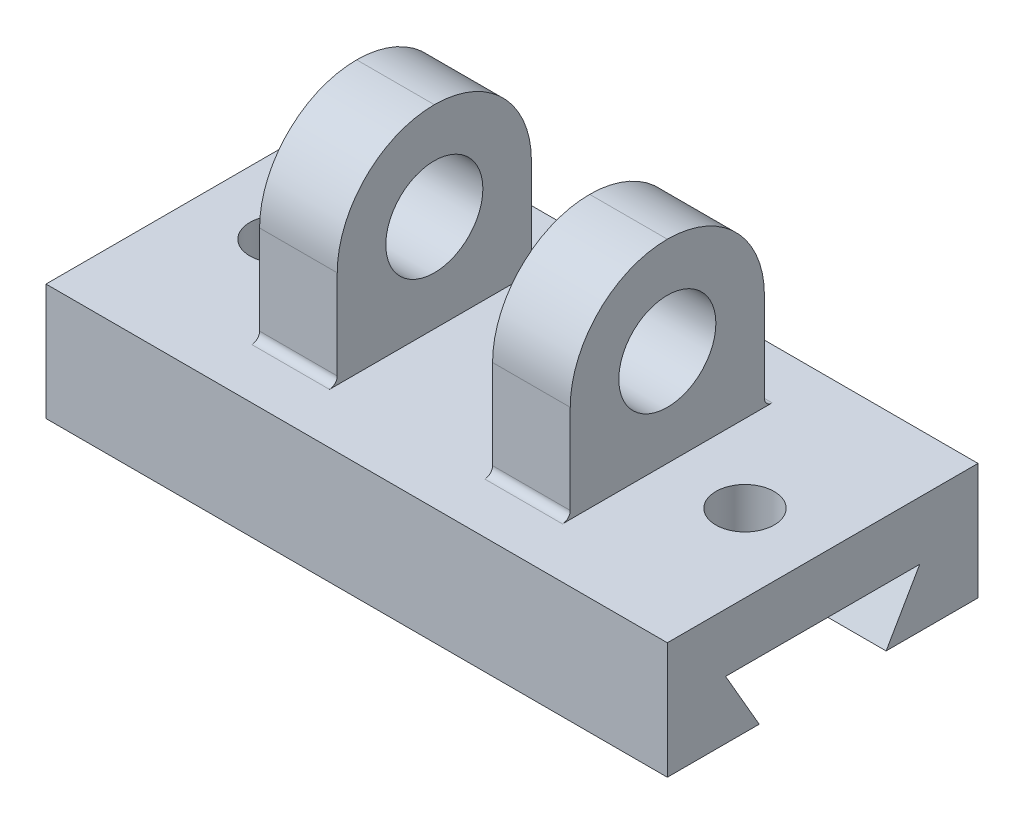
SolidWorks part; units mm, degrees
ref_plane "Front Plane" through (0, 0, 0) normal (0, 0, 1) x (1, 0, 0)
ref_plane "Top Plane" through (0, 0, 0) normal (0, 1, 0) x (1, 0, 0)
ref_plane "Right Plane" through (0, 0, 0) normal (1, 0, 0) x (0, 0, -1)
sketch "Sketch1" plane through (0, 0, 0) normal (1, 0, 0) x (0, 0, -1)
  line L0 (0, 0) -> (-80, 0)
  line L1 (-80, 0) -> (-80, -30)
  line L2 (-80, -30) -> (-56.3397, -30)
  line L3 (-56.3397, -30) -> (-65, -15)
  line L4 (-65, -15) -> (-15, -15)
  line L5 (-15, -15) -> (-23.6603, -30)
  line L6 (-23.6603, -30) -> (0, -30)
  line L7 (0, -30) -> (0, 0)
  point P7 (-80, -15)
  point P10 (0, 0)
  dimension "D1" = 80
  dimension "D2" = 15
  dimension "D3" = 30
  dimension "D4" = 15
  dimension "D5" = 30
  dimension "D6" = 60
  dimension "D7" = 60
  dimension "D8" = 15
extrude "Boss-Extrude2" add sketch "Sketch1" along normal blind 80
sketch "Sketch3" plane through (0, 0, 0) normal (0, 1, 0) x (1, 0, 0)
  line L0 (40, -15) -> (40, -65)
  line L1 (40, -65) -> (20, -65)
  line L2 (20, -65) -> (20, -15)
  line L3 (20, -15) -> (40, -15)
  line L4 (80, 0) -> (80, -80) construction
  point P6 (40, -40)
  point P7 (80, -40)
  dimension "D1" = 40
  dimension "D2" = 20
  dimension "D3" = 50
  dimension "D4" = 0
extrude "Boss-Extrude3" add sketch "Sketch3" along normal blind 50
fillet "Fillet3" radius 25 2 edges at (30, 50, 65) (30, 50, 15)
sketch "Sketch8" plane through (40, 0, 0) normal (1, 0, 0) x (0, 0, -1)
  circle A2 centre (-40, 25) radius 12.5
extrude "Cut-Extrude1" cut sketch "Sketch8" against normal blind 50
sketch "Sketch9" plane through (0, 0, 0) normal (0, 1, 0) x (1, 0, 0)
  line L0 (80, 0) -> (0, 0) construction
  line L1 (40, -65) -> (40, -15) construction
  circle A0 centre (60, -40) radius 7.5
  point P6 (0, 0)
  dimension "D1" = 40
  dimension "D2" = 20
extrude "Cut-Extrude3" cut sketch "Sketch9" against normal blind 50
fillet "Fillet4" radius 2 1 edges at (30, 0, 65)
fillet "Fillet5" radius 2 1 edges at (30, 0, 15)
mirror "Mirror14" about plane through (0, 0, 0) normal (1, 0, 0) of "Fillet5", "Fillet4", "Cut-Extrude3", "Cut-Extrude1", "Fillet3", "Boss-Extrude3", "Boss-Extrude2"
